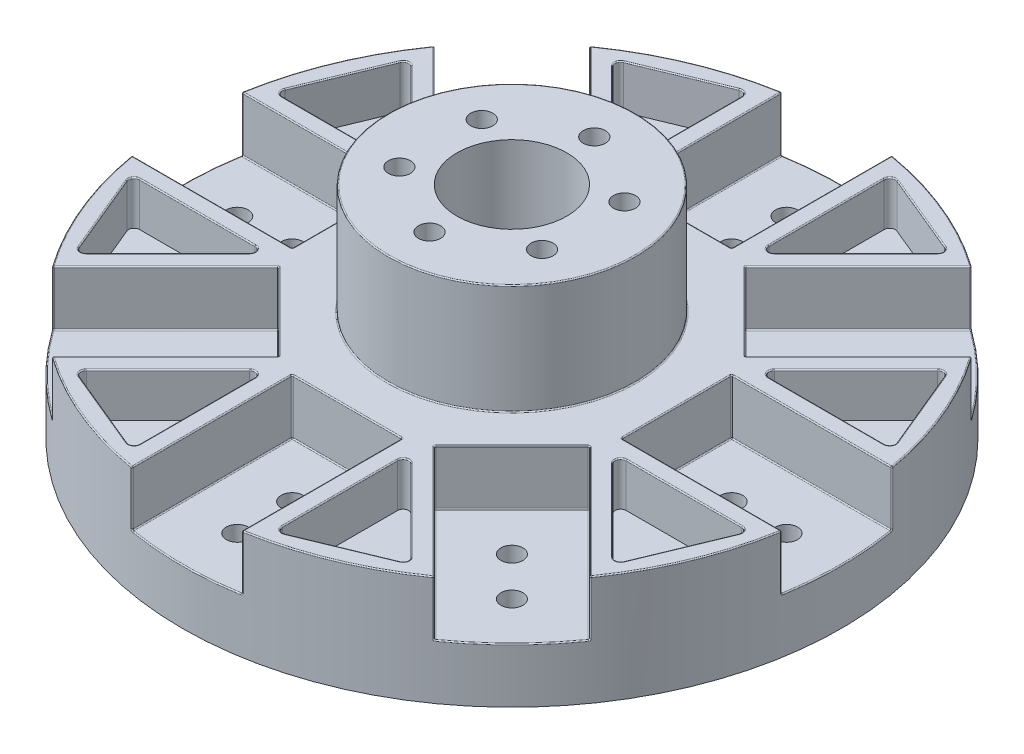
SolidWorks part; units mm, degrees
note: '?' marks a value the reader was unsure of.
material "AISI 1010 Steel, hot rolled bar"
ref_plane "Front Plane" through (0, 0, 0) normal (0, 0, 1) x (1, 0, 0)
ref_plane "Top Plane" through (0, 0, 0) normal (0, 1, 0) x (1, 0, 0)
ref_plane "Right Plane" through (0, 0, 0) normal (1, 0, 0) x (0, 0, -1)
sketch "Sketch2" plane through (0, 0, 0) normal (0, 1, 0) x (1, 0, 0)
  circle A0 centre (0, 0) radius 76.2
  dimension "D1" = 152.4
extrude "Boss-Extrude1" add sketch "Sketch2" along normal blind 25.4
sketch "Sketch4" plane through (0, 25.4, 0) normal (0, 1, 0) x (1, 0, 0)
  circle A0 centre (0, 0) radius 28.575
  dimension "D1" = 57.15
extrude "Boss-Extrude2" add sketch "Sketch4" along normal blind 25.4
sketch "Sketch3" plane through (0, 25.4, 0) normal (0, 1, 0) x (1, 0, 0)
  line L1 (-12.7, -38.1) -> (12.7, -38.1)
  line L2 (-12.7, -38.1) -> (-12.7, -114.3)
  line L3 (-12.7, -114.3) -> (12.7, -114.3)
  line L4 (12.7, -38.1) -> (12.7, -114.3)
  line L5 (-12.7, -38.1) -> (12.7, -114.3) construction
  line L6 (-12.7, -114.3) -> (12.7, -38.1) construction
  point P0 (0, -76.2)
  point P5 (0, 0)
  dimension "D1" = 38.1
  dimension "D2" = 25.4
  dimension "D3" = 76.2
extrude "Cut-Extrude1" cut sketch "Sketch3" against normal blind 12.7
ref_axis "Axis1" through (0, 25.4, 0) along (0, -1, 0)?
pattern_circular "CirPattern1" count 8 over 360 about axis through (0, 0, 0) along (0, 1, 0) of "Cut-Extrude1"
sketch "Sketch5" plane through (0, 50.8, 0) normal (0, 1, 0) x (1, 0, 0)
  circle A0 centre (0, 0) radius 12.7
  dimension "D1" = 25.4
extrude "Cut-Extrude2" cut sketch "Sketch5" against normal through all
sketch "Sketch7" plane through (0, 25.4, 0) normal (0, 1, 0) x (1, 0, 0)
  line L5 (0, 0) -> (-29.1605, -70.3996) construction
  line L6 (-18.678, -42.0267) -> (-37.5224, -60.871)
  line L7 (-37.1104, -62.9424) -> (-18.266, -70.748)
  line L8 (-16.51, -69.5747) -> (-16.51, -42.9247)
  line L9 (-12.7, -38.1) -> (-12.7, -75.1342) construction
  line L10 (-44.1477, -62.1082) -> (-17.9605, -35.921) construction
  arc A3 (-44.1477, -62.1082) -> (-12.7, -75.1342) centre (0, 0) ccw construction
  arc A4 (-37.5224, -60.871) -> (-37.1104, -62.9424) centre (-36.6244, -61.7691) ccw
  arc A5 (-18.678, -42.0267) -> (-16.51, -42.9247) centre (-17.78, -42.9247) cw
  arc A6 (-18.266, -70.748) -> (-16.51, -69.5747) centre (-17.78, -69.5747) ccw
  point P1 (-17.6871, -42.7004)
  point P12 (-18.1317, -43.7739)
  point P13 (-15.8021, -70.3996)
  point P20 (-16.51, -39.8587)
  dimension "D1" = 29.21
  dimension "D3" = 1.27
  dimension "D2" = 3.81
extrude "Cut-Extrude3" cut sketch "Sketch7" against normal blind 10.16
pattern_circular "CirPattern2" count 8 over 360 about axis through (0, 0, 0) along (0, 1, 0) of "Cut-Extrude3"
hole_wizard "Tap Drill for 1/4-20 Tap1" positions "Sketch9" profile "Sketch10" hole size "1/4-20" standard "ANSI Inch"
sketch "Sketch9" plane through (0, 50.8, 0) normal (0, 1, 0) x (1, 0, 0)
  point P0 (0, 19.05)
  dimension "D1" = 19.05
sketch "Sketch10" plane through (0, 50.8, -19.05) normal (1, 0, 0) x (0, 0, 1)
  line L0 (0, 0) -> (0, 14.2338)
  line L1 (0, 14.2338) -> (2.5527, 12.7)
  line L2 (2.5527, 12.7) -> (2.5527, 0)
  line L5 (2.5527, 0) -> (0, 0)
  line L10 (0, 14.2338) -> (-2.5527, 12.7) construction
  line L11 (0, -6.35) -> (0, 107.95) construction
  dimension "Hole Dia." = 5.1054
  dimension "Hole Depth" = 12.7
  dimension "Drill Angle" = 118
pattern_circular "CirPattern3" count 6 over 360 about axis through (0, 0, 0) along (0, 1, 0) of "Tap Drill for 1/4-20 Tap1"
sketch "Sketch11" plane through (0, 12.7, 0) normal (0, 1, 0) x (1, 0, 0)
  circle A0 centre (0, -50.8) radius 2.54
  circle A1 centre (0, -63.5) radius 2.54
  point P4 (0, 0)
  point P6 (0, 0)
  dimension "D2" = 5.08
  dimension "D3" = 50.8
  dimension "D4" = 12.7
extrude "Cut-Extrude5" cut sketch "Sketch11" against normal through all
pattern_circular "CirPattern4" count 8 over 360 about axis through (0, 0, 0) along (0, 1, 0) of "Cut-Extrude5"
fillet "Fillet1" radius 0.254 113 edges at (-62.1082, 19.05, 44.1477) (12.7, 19.05, -75.1342) (-12.7, 19.05, -75.1342) (44.1477, 19.05, -62.1082) (75.1342, 19.05, 12.7) (75.1342, 19.05, -12.7) (44.1477, 19.05, 62.1082) (62.1082, 19.05, 44.1477) (-44.1477, 19.05, -62.1082) (-62.1082, 19.05, -44.1477) (-75.1342, 19.05, -12.7) (-53.8815, 12.7, 53.8815) (12.7, 12.7, -56.6171) (0, 12.7, -76.2) (0, 12.7, -38.1) (-12.7, 12.7, -56.6171) (31.0541, 12.7, -49.0146) (49.0146, 12.7, -31.0541) (53.8815, 12.7, -53.8815) (56.6171, 12.7, 12.7) (38.1, 12.7, 0) (76.2, 12.7, 0) (53.8815, 12.7, 53.8815) (49.0146, 12.7, 31.0541) (31.0541, 12.7, 49.0146) (12.7, 12.7, 56.6171) (0, 12.7, 38.1) (-12.7, 19.05, 75.1342) (-12.7, 12.7, 56.6171) (-31.0541, 12.7, -49.0146) (-49.0146, 12.7, -31.0541) (-53.8815, 12.7, -53.8815) (-26.9408, 12.7, -26.9408) (-56.6171, 12.7, 12.7) (-38.1, 12.7, 0) (-56.6171, 12.7, -12.7) (-44.1477, 19.05, 62.1082) (-31.0541, 12.7, 49.0146) (-26.9408, 12.7, 26.9408) (-49.0146, 12.7, 31.0541) (0, 50.8, 28.575) (-38.1, 25.4, 0) (-56.6171, 25.4, -12.7) (-49.0146, 25.4, -31.0541) (-26.9408, 25.4, -26.9408) (-31.0541, 25.4, -49.0146) (-29.1605, 25.4, -70.3996) (-12.7, 25.4, -56.6171) (0, 25.4, -38.1) (12.7, 25.4, -56.6171) (29.1605, 25.4, -70.3996) (31.0541, 25.4, -49.0146) (49.0146, 25.4, -31.0541) (70.3996, 25.4, -29.1605) (38.1, 25.4, 0) (56.6171, 25.4, 12.7) (70.3996, 25.4, 29.1605) (49.0146, 25.4, 31.0541) (26.9408, 25.4, 26.9408) (31.0541, 25.4, 49.0146) (29.1605, 25.4, 70.3996) (12.7, 25.4, 56.6171) (0, 25.4, 38.1) (-31.0541, 25.4, 49.0146) (-26.9408, 25.4, 26.9408) (-49.0146, 25.4, 31.0541) (-70.3996, 25.4, 29.1605) (-56.6171, 25.4, 12.7) (-27.6882, 25.4, 66.8452) (-17.0744, 25.4, 70.6306) (-16.51, 25.4, 56.2497) (-37.8699, 25.4, 62.0168) (-66.8452, 25.4, 27.6882) (-62.0168, 25.4, 37.8699) (-51.4489, 25.4, 28.1002) (-41.7514, 25.4, 17.294) (-56.2497, 25.4, 16.51) (-70.6306, 25.4, 17.0744) (-56.2497, 25.4, -16.51) (-41.7514, 25.4, -17.294) (-51.4489, 25.4, -28.1002) (-62.0168, 25.4, -37.8699) (-27.6882, 25.4, -66.8452) (-37.8699, 25.4, -62.0168) (-28.1002, 25.4, -51.4489) (-17.294, 25.4, -41.7514) (-17.0744, 25.4, -70.6306) (17.0744, 25.4, -70.6306) (16.51, 25.4, -56.2497) (28.1002, 25.4, -51.4489) (37.8699, 25.4, -62.0168) (62.0168, 25.4, -37.8699) (70.6306, 25.4, 17.0744) (56.2497, 25.4, 16.51) (41.7514, 25.4, 17.294) (51.4489, 25.4, 28.1002) (62.0168, 25.4, 37.8699) (27.6882, 25.4, 66.8452) (37.8699, 25.4, 62.0168) (28.1002, 25.4, 51.4489) (17.294, 25.4, 41.7514) (17.0744, 25.4, 70.6306) (35.921, 19.05, 17.9605) (12.7, 19.05, 38.1) (-12.7, 19.05, 38.1) (-35.921, 19.05, 17.9605) (-38.1, 19.05, 12.7) (-35.921, 19.05, -17.9605) (-17.9605, 19.05, -35.921) (-12.7, 19.05, -38.1) (12.7, 19.05, -38.1) (17.9605, 19.05, -35.921) (38.1, 19.05, -12.7)
